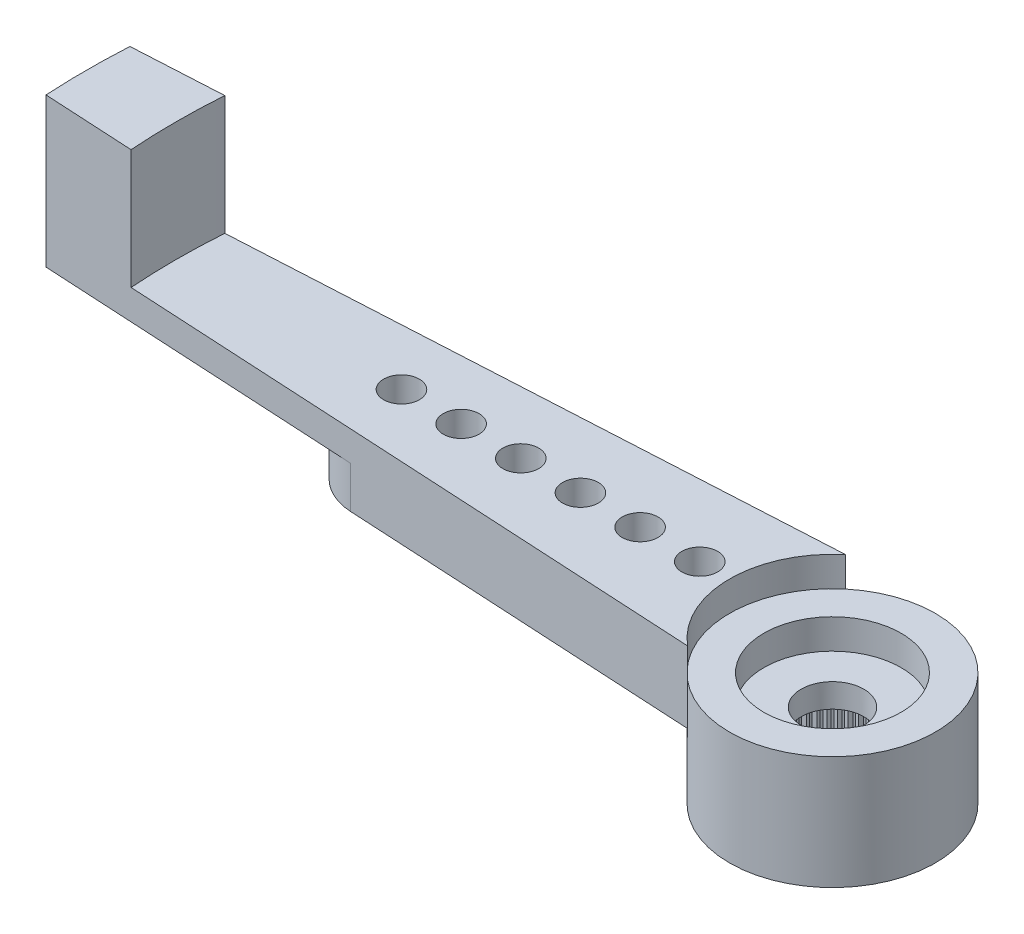
SolidWorks part; units mm, degrees
material "PVC Rígido"
ref_plane "Plano frontal" through (0, 0, 0) normal (0, 0, 1) x (1, 0, 0)
ref_plane "Plano superior" through (0, 0, 0) normal (0, 1, 0) x (1, 0, 0)
ref_plane "Plano direito" through (0, 0, 0) normal (1, 0, 0) x (0, 0, -1)
sketch "Esboço1" plane through (0, 0, 0) normal (0, 1, 0) x (1, 0, 0)
  line L0 (0, 0) -> (-14.05, 0) construction
  line L1 (-14.1591, 1.997) -> (-2.2091, 2.65)
  line L2 (-2.2091, -2.65) -> (-14.1591, -1.997)
  arc A0 (-2.2091, -2.65) -> (-2.2091, 2.65) centre (0, 0) ccw
  arc A1 (-14.1591, 1.997) -> (-14.1591, -1.997) centre (-14.05, 0) ccw
  dimension "D1" = 6.9
  dimension "D2" = 4
  dimension "D3" = 19.5
  dimension "D4" = 5.3
extrude "Ressalto-extrusão1" add sketch "Esboço1" against normal blind 1.4
sketch "Esboço2" plane through (0, -1.4, 0) normal (0, -1, 0) x (1, 0, 0)
  arc A0 (-2.2091, -2.65) -> (-2.2091, 2.65) centre (0, 0) ccw construction
  circle A1 centre (0, 0) radius 3.45
extrude "Ressalto-extrusão2" add sketch "Esboço2" along normal offset from surface (2.4 mm away) 3.8 up to face at (-7.242, 0, 0)
hole_wizard "Furo4" positions "Esboço9" profile "Esboço10" legacy end condition through all
sketch "Esboço9" plane through (0, 0, 0) normal (0, 1, 0) x (1, 0, 0)
  line L1 (-14.45, 0) -> (0, 0) construction
  arc A2 (-14.1591, 1.997) -> (-14.1591, -1.997) centre (-14.05, 0) ccw construction
  point P0 (-14.45, 0)
  point P19 (-16.05, 0)
  dimension "D1" = 1.6
sketch "Esboço10" plane through (-14.45, 0, 0) normal (1, 0, 0) x (0, 0, 1)
  line L0 (0, 0) -> (0, 3.8)
  line L1 (0, 3.8) -> (0.6, 3.8)
  line L2 (0.6, 3.8) -> (0.6, 0)
  line L3 (0.6, 0) -> (0, 0)
  line L4 (0, 110) -> (0, -10) construction
  dimension "Diameter" = 1.2
  dimension "Depth" = 3.8
pattern_linear "Padrão linear1" count 6 spacing 2 along (1, 0, 0) of "Furo4"
hole_wizard "Furo1" positions "Esboço3" profile "Esboço4" legacy
sketch "Esboço3" plane through (0, -3.8, 0) normal (0, -1, 0) x (-1, 0, 0)
  point P0 (0, 0)
sketch "Esboço4" plane through (0, -3.8, 0) normal (1, 0, 0) x (0, 0, -1)
  line L0 (0, 0) -> (0, 2)
  line L1 (0, 2) -> (2.475, 2)
  line L2 (2.475, 2) -> (2.475, 0)
  line L3 (2.475, 0) -> (0, 0)
  line L4 (0, 110) -> (0, -10) construction
  dimension "Diameter" = 4.95
  dimension "Depth" = 2
hole_wizard "Furo2" positions "Esboço5" profile "Esboço6" legacy
sketch "Esboço5" plane through (0, 0, 0) normal (0, 1, 0) x (1, 0, 0)
  point P0 (0, 0)
sketch "Esboço6" plane through (0, 0, 0) normal (1, 0, 0) x (0, 0, 1)
  line L0 (0, 0) -> (0, 1)
  line L1 (0, 1) -> (2.3, 1)
  line L2 (2.3, 1) -> (2.3, 0)
  line L3 (2.3, 0) -> (0, 0)
  line L4 (0, 110) -> (0, -10) construction
  dimension "Diameter" = 4.6
  dimension "Depth" = 1
hole_wizard "Furo3" positions "Esboço7" profile "Esboço8" legacy end condition through all
sketch "Esboço7" plane through (0, 0, 0) normal (0, 1, 0) x (1, 0, 0)
  point P0 (0, 0)
sketch "Esboço8" plane through (0, 0, 0) normal (1, 0, 0) x (0, 0, 1)
  line L0 (0, 0) -> (0, 3.8)
  line L1 (0, 3.8) -> (1.05, 3.8)
  line L2 (1.05, 3.8) -> (1.05, 0)
  line L3 (1.05, 0) -> (0, 0)
  line L4 (0, 110) -> (0, -10) construction
  dimension "Diameter" = 2.1
  dimension "Depth" = 3.8
sketch "Esboço11" plane through (0, -3.8, 0) normal (0, -1, 0) x (1, 0, 0)
  line L0 (-0.0981, 2.4731) -> (0, 2.375)
  line L1 (0, 2.375) -> (0.0981, 2.4731)
  line L2 (0, 0) -> (0, 2.475) construction
  circle A0 centre (0, 0) radius 2.375 construction
  circle A1 centre (0, 0) radius 2.475
  arc A2 (0.0981, 2.4731) -> (-0.0981, 2.4731) centre (0, 0) ccw
  dimension "D3" = 4.75
  dimension "D2" = 0.1
  dimension "D1" = 0
extrude "Ressalto-extrusão3" add sketch "Esboço11" against normal up to surface (2 mm away) up to face at (0, -1.8, 1.05)
pattern_circular "PadrãoCircular1" count 60 over 360 about axis through (0, -1.4, 0) along (0, 1, 0) of "Ressalto-extrusão3"
sketch "Sketch1" plane through (0, 0, 0) normal (0, 1, 0) x (1, 0, 0)
  line L0 (0, 0) -> (-20.516, 0) construction
  line L1 (0, 0) -> (0, 6.2035) construction
  line L2 (-2.2091, 2.65) -> (-14.1591, 1.997)
  line L3 (-14.1591, 1.997) -> (-24.9604, 1.4068)
  line L4 (-2.2091, -2.65) -> (-14.1591, -1.997)
  line L5 (-14.1591, -1.997) -> (-24.9604, -1.4068)
  arc A0 (-24.9604, 1.4068) -> (-24.9604, -1.4068) centre (0, 0) ccw
  arc A1 (-21.9438, 1.5716) -> (-21.9438, -1.5716) centre (0, 0) ccw
  arc A8 (-2.2091, 2.65) -> (-2.2091, -2.65) centre (0, 0) ccw
  circle M11 centre (-12.45, 0) radius 0.6
  circle M12 centre (-14.45, 0) radius 0.6
  line M14 (-2.2091, 2.65) -> (-14.1591, 1.997)
  arc M15 (-14.1591, 1.997) -> (-14.1591, -1.997) centre (-14.05, 0) ccw
  line M16 (-14.1591, -1.997) -> (-2.2091, -2.65)
  circle M17 centre (-10.45, 0) radius 0.6
  circle M18 centre (-8.45, 0) radius 0.6
  circle M19 centre (-6.45, 0) radius 0.6
  circle M20 centre (-4.45, 0) radius 0.6
  dimension "D1" = 10.8013
  dimension "D2" = 44
extrude "Boss-Extrude2" add sketch "Sketch1" along normal blind 5 separate body contours A1 L3 A0 L5 region at (-23.4564, 0, 0)
extrude "Boss-Extrude3" add sketch "Sketch1<4>" along normal blind 1 contours L3 A1 L5 M15 | A8 M14 M15 M16 M11 M18 M20 M19 M17 M12 region at (-3.5982, 0, 0) region at (-18.6977, 0, 0)
sketch "Sketch1<4>" plane through (0, 0, 0) normal (0, 1, 0) x (1, 0, 0) same geometry as "Sketch1"
